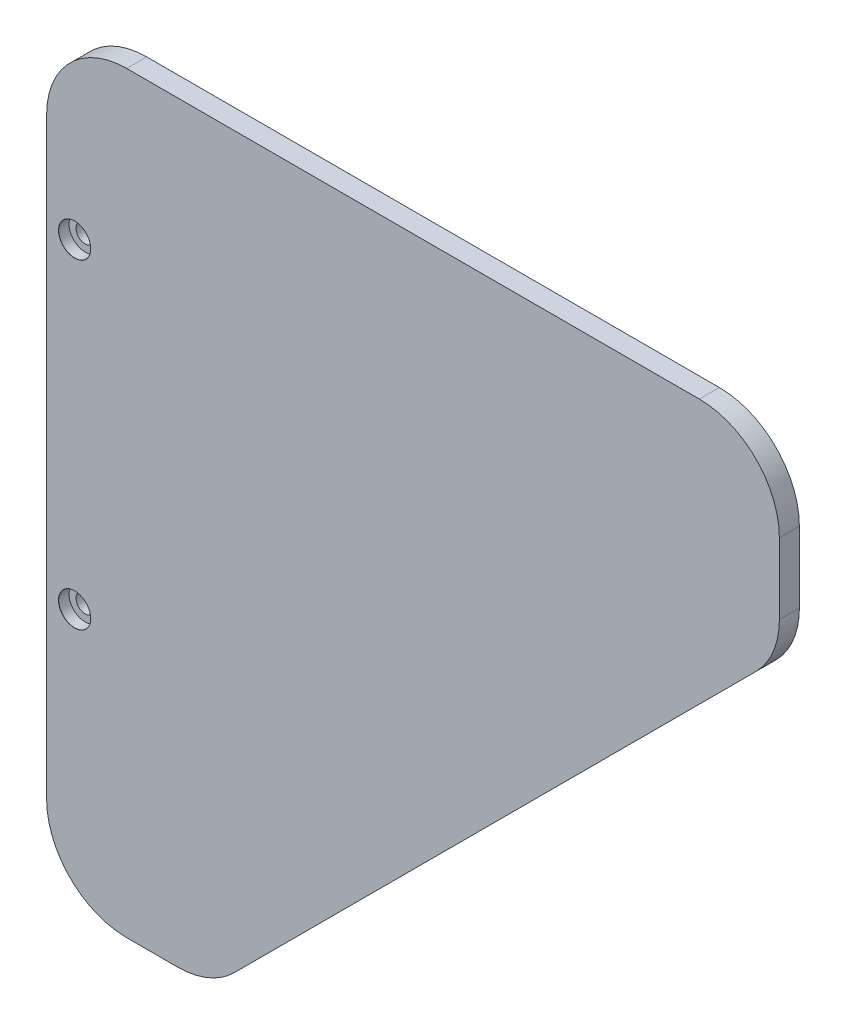
SolidWorks part; units mm, degrees
ref_plane "Piano frontale" through (0, 0, 0) normal (0, 0, 1) x (1, 0, 0)
ref_plane "Piano superiore" through (0, 0, 0) normal (0, 1, 0) x (1, 0, 0)
ref_plane "Piano destro" through (0, 0, 0) normal (1, 0, 0) x (0, 0, -1)
sketch "Schizzo1" plane through (0, 0, 0) normal (0, 0, 1) x (1, 0, 0)
  line L0 (0, 20) -> (0, 168)
  line L1 (20, 188) -> (163, 188)
  line L2 (183, 168) -> (183, 150.2843)
  line L3 (177.1421, 136.1421) -> (46.8579, 5.8579)
  line L4 (32.7157, 0) -> (20, 0)
  arc A0 (0, 168) -> (20, 188) centre (20, 168) cw
  arc A1 (0, 20) -> (20, 0) centre (20, 20) ccw
  arc A2 (46.8579, 5.8579) -> (32.7157, 0) centre (32.7157, 20) cw
  arc A3 (183, 150.2843) -> (177.1421, 136.1421) centre (163, 150.2843) cw
  arc A4 (163, 188) -> (183, 168) centre (163, 168) cw
  point P8 (0, 188)
  point P11 (0, 0)
  point P14 (41, 0)
  point P17 (183, 142)
  point P20 (183, 188)
  dimension "D5" = 20
  dimension "D1" = 183
  dimension "D2" = 46
  dimension "D3" = 45
  dimension "D4" = 41
extrude "Estrusione-Estrusione1" add sketch "Schizzo1" along normal blind 5
hole_wizard "Foro lamato per Vite M4 a testa cilindrica piana-1" positions "Schizzo3" profile "Schizzo4" counterbore size "M4" standard "ISO" end condition through all
sketch "Schizzo3" plane through (0, 0, 5) normal (0, 0, 1) x (1, 0, 0)
  line L0 (0, 168) -> (0, 20) construction
  line L1 (163, 188) -> (20, 188) construction
  point P0 (7, 144.5)
  point P2 (7, 64.5)
  dimension "D1" = 80
  dimension "D2" = 7
  dimension "D3" = 43.5
sketch "Schizzo4" plane through (7, 144.5, 5) normal (1, 0, 0) x (0, -1, 0)
  line L0 (0, 0) -> (0, 5)
  line L1 (0, 5) -> (2.25, 5)
  line L3 (2.25, 5) -> (2.25, 2.6)
  line L4 (4, 2.6) -> (2.25, 2.6)
  line L5 (4, 2.6) -> (4, 0.025)
  line L6 (4, 0.025) -> (4.025, 0)
  line L7 (4.025, 0) -> (0, 0)
  line L8 (-4, 0.025) -> (-4.025, 0) construction
  line L11 (0, -6.35) -> (0, 107.95) construction
  dimension "Thru Hole Dia." = 4.5
  dimension "Thru Hole Depth" = 5
  dimension "C'Bore Dia." = 8
  dimension "C'Bore Depth" = 2.6
  dimension "Near C'Sink Dia." = 8.05
  dimension "Near C'Sink Angle" = 90
